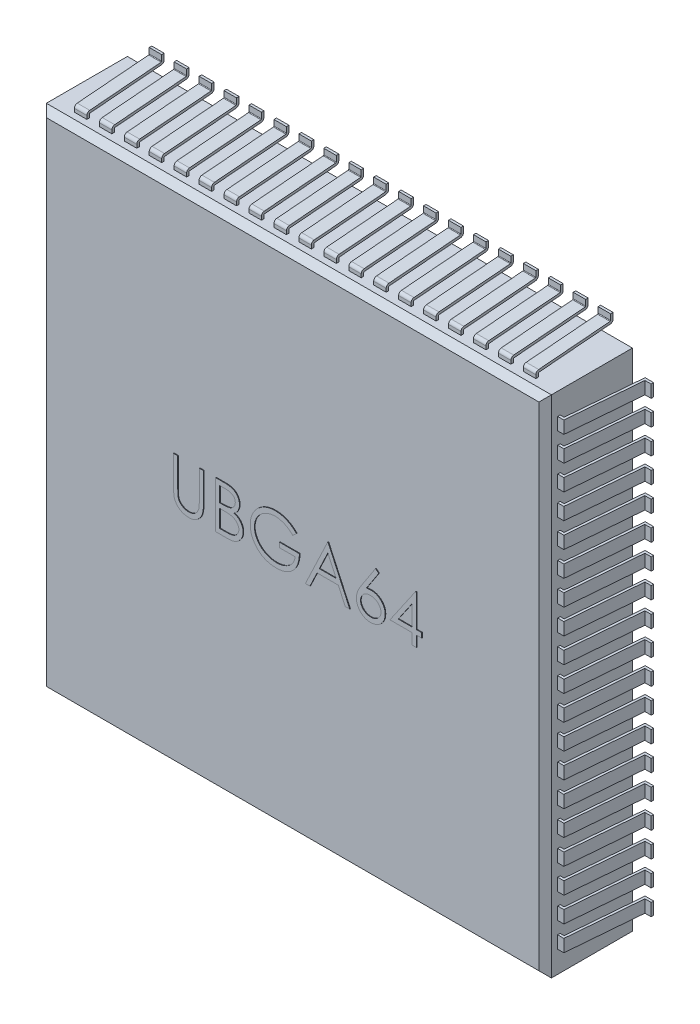
SolidWorks part; units mm, degrees
ref_plane "Front" through (0, 0, 0) normal (0, 0, 1) x (1, 0, 0)
ref_plane "Top" through (0, 0, 0) normal (0, 1, 0) x (1, 0, 0)
ref_plane "Right" through (0, 0, 0) normal (1, 0, 0) x (0, 0, -1)
sketch "COMPONENT_OUTLINE" plane through (0, 0, 0) normal (0, 0, 1) x (1, 0, 0)
  line L0 (-4.05, 4.05) -> (-4.05, -4.05)
  line L1 (-4.05, -4.05) -> (4.05, -4.05)
  line L2 (4.05, -4.05) -> (4.05, 4.05)
  line L3 (4.05, 4.05) -> (-4.05, 4.05)
extrude "Extrude1" add sketch "COMPONENT_OUTLINE" along normal blind 1.4
sketch "Sketch1" plane through (0, 0, 0) normal (1, 0, 0) x (0, 0, -1)
  line L0 (-1.2, 4.05) -> (-1.2, 4.15)
  line L1 (-1.4, 4.05) -> (0, 4.05) construction
  line L2 (-1.2, 4.15) -> (0, 4.25)
  line L3 (0, 4.25) -> (0, 4.35)
  dimension "D1" = 0.1
  dimension "D2" = 0.2
  dimension "D3" = 0.2
  dimension "D4" = 0.1
extrude "Extrude-Thin1" add sketch "Sketch1" along normal mid plane 0.2 thin thin type one direction wall 0.04
pattern_linear "LPattern1" count 10 spacing 0.4 along (-1, 0, 0) count 10 spacing 0.4 along (1, 0, 0) of "Extrude-Thin1"
mirror "Mirror1" about plane through (0, 0, 0) normal (0, 1, 0) of "Extrude-Thin1", "LPattern1"
sketch "Sketch2" plane through (0, 0, 0) normal (0, 1, 0) x (1, 0, 0)
  line L0 (4.05, -1.2) -> (4.15, -1.2)
  line L1 (4.05, -1.4) -> (4.05, 0) construction
  line L2 (4.15, -1.2) -> (4.25, 0)
  line L3 (4.25, 0) -> (4.35, 0)
  line L4 (4.05, -1.4) -> (-4.05, -1.4) construction
  dimension "D1" = 0.1
  dimension "D2" = 0.2
  dimension "D3" = 0.2
  dimension "D4" = 0.1
extrude "Extrude-Thin2" add sketch "Sketch2" along normal mid plane 0.2 thin thin type one direction reverse wall 0.04
pattern_linear "LPattern2" count 10 spacing 0.4 along (0, 1, 0) count 10 spacing 0.4 along (0, -1, 0) of "Extrude-Thin2"
mirror "Mirror2" about plane through (0, 0, 0) normal (1, 0, 0) of "LPattern2"
chamfer "Chamfer1" distance 0.1 angle 45 4 edges at (4.05, 0, 1.4) (0, -4.05, 1.4) (-4.05, 0, 1.4) (0, 4.05, 1.4)
sketch "Sketch3" plane through (0, 0, 1.4) normal (0, 0, 1) x (1, 0, 0)
  text T0 "UBGA64" font "Century Gothic" height 0.75
extrude "Extrude2" add sketch "Sketch3" along normal blind 0.01
